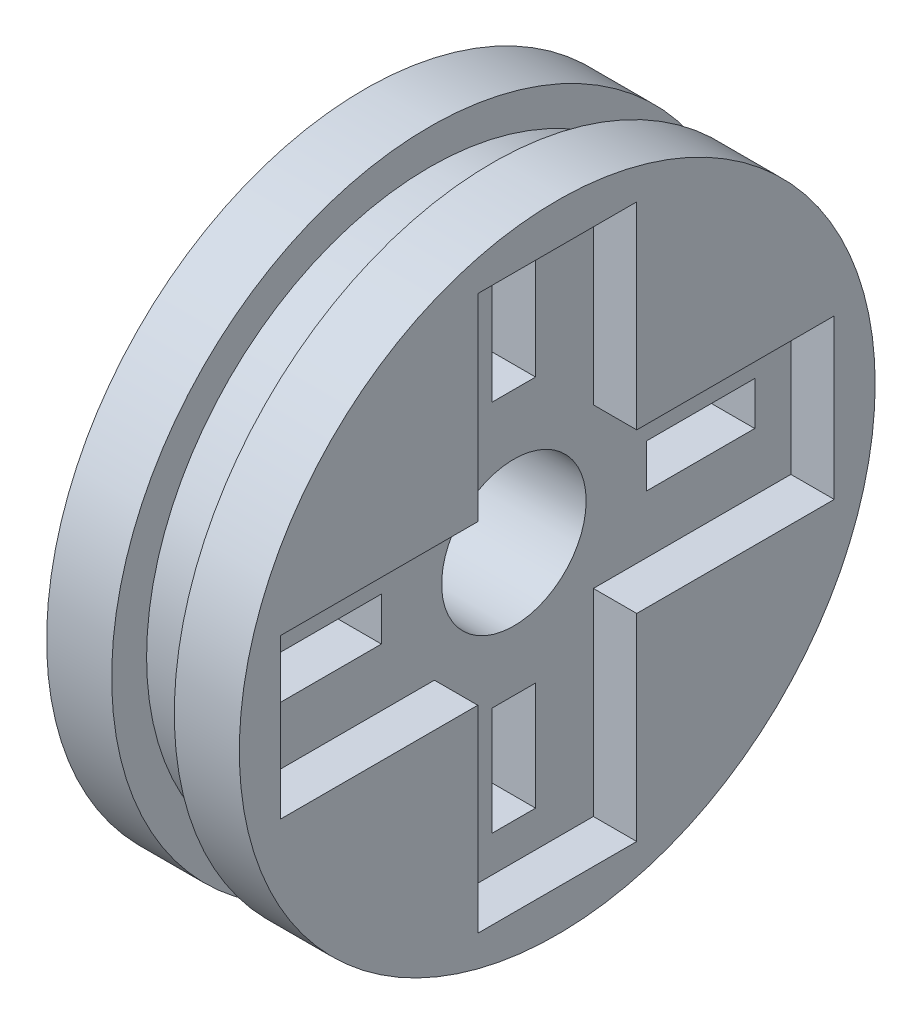
SolidWorks part; units mm, degrees
ref_plane "Front Plane" through (0, 0, 0) normal (0, 0, 1) x (1, 0, 0)
ref_plane "Top Plane" through (0, 0, 0) normal (0, 1, 0) x (1, 0, 0)
ref_plane "Right Plane" through (0, 0, 0) normal (1, 0, 0) x (0, 0, -1)
sketch "Sketch1" plane through (0, 0, 0) normal (1, 0, 0) x (0, 0, -1)
  circle A0 centre (-66, -65) radius 13.2
extrude "Boss-Extrude1" add sketch "Sketch1" along normal blind 8 from offset 85.2 offset against normal yes
sketch "Sketch2" plane through (0, 0, 0) normal (1, 0, 0) x (0, 0, -1)
  circle A0 centre (-66, -65) radius 20
extrude "Boss-Extrude2" add sketch "Sketch2" along normal blind 2.6 from offset 82.5 separate body offset against normal yes
combine bodies "Combine1" operation type subtract main body 101 bodies to subtract 102
sketch "Sketch3" plane through (0, 0, 0) normal (1, 0, 0) x (0, 0, -1)
  circle A0 centre (-66, -65) radius 11.75
extrude "Boss-Extrude3" add sketch "Sketch3" along normal blind 2.6 from offset 82.5 offset against normal yes
sketch "Sketch4" plane through (0, 0, 0) normal (1, 0, 0) x (0, 0, -1)
  circle A0 centre (-66, -65) radius 4.6
extrude "Boss-Extrude4" add sketch "Sketch4" along normal blind 2.3 from offset 79 separate body offset against normal yes
combine bodies "Combine2" operation type subtract main body 105 bodies to subtract 106
sketch "Sketch5" plane through (0, 0, 0) normal (0, 0, 1) x (1, 0, 0)
  line L1 (-79, -65) -> (-76.7, -65)
  line L2 (-79, -65) -> (-79, -53.5)
  line L3 (-79, -53.5) -> (-76.7, -53.5)
  line L4 (-76.7, -65) -> (-76.7, -53.5)
extrude "Boss-Extrude5" add sketch "Sketch5" along normal blind 6.6 from offset 62.7 separate body
combine bodies "Combine3" operation type subtract main body 107 bodies to subtract 108
sketch "Sketch6" plane through (0, 0, 0) normal (0, 0, 1) x (1, 0, 0)
  line L1 (-86.2, -59.5) -> (-76.2, -59.5)
  line L2 (-86.2, -59.5) -> (-86.2, -55)
  line L3 (-86.2, -55) -> (-76.2, -55)
  line L4 (-76.2, -59.5) -> (-76.2, -55)
extrude "Boss-Extrude6" add sketch "Sketch6" along normal blind 1.8 from offset 65.1 separate body
combine bodies "Combine4" operation type subtract main body 109 bodies to subtract 110
sketch "Sketch7" plane through (0, 0, 0) normal (0, 0, 1) x (1, 0, 0)
  line L1 (-79, -76.5) -> (-76.7, -76.5)
  line L2 (-79, -76.5) -> (-79, -65)
  line L3 (-79, -65) -> (-76.7, -65)
  line L4 (-76.7, -76.5) -> (-76.7, -65)
extrude "Boss-Extrude7" add sketch "Sketch7" along normal blind 6.6 from offset 62.7 separate body
combine bodies "Combine5" operation type subtract main body 111 bodies to subtract 112
sketch "Sketch8" plane through (0, 0, 0) normal (0, 0, 1) x (1, 0, 0)
  line L1 (-86.2, -75) -> (-76.2, -75)
  line L2 (-86.2, -75) -> (-86.2, -70.5)
  line L3 (-86.2, -70.5) -> (-76.2, -70.5)
  line L4 (-76.2, -75) -> (-76.2, -70.5)
extrude "Boss-Extrude8" add sketch "Sketch8" along normal blind 1.8 from offset 65.1 separate body
combine bodies "Combine6" operation type subtract main body 113 bodies to subtract 114
sketch "Sketch9" plane through (0, 0, 0) normal (0, 0, 1) x (1, 0, 0)
  line L1 (-79, -68.3) -> (-76.7, -68.3)
  line L2 (-79, -68.3) -> (-79, -61.7)
  line L3 (-79, -61.7) -> (-76.7, -61.7)
  line L4 (-76.7, -68.3) -> (-76.7, -61.7)
extrude "Boss-Extrude9" add sketch "Sketch9" along normal blind 11.5 from offset 66 separate body
combine bodies "Combine7" operation type subtract main body 115 bodies to subtract 116
sketch "Sketch10" plane through (0, 0, 0) normal (0, 0, 1) x (1, 0, 0)
  line L1 (-86.2, -65.9) -> (-76.2, -65.9)
  line L2 (-86.2, -65.9) -> (-86.2, -64.1)
  line L3 (-86.2, -64.1) -> (-76.2, -64.1)
  line L4 (-76.2, -65.9) -> (-76.2, -64.1)
extrude "Boss-Extrude10" add sketch "Sketch10" along normal blind 4.5 from offset 71.5 separate body
combine bodies "Combine8" operation type subtract main body 117 bodies to subtract 118
sketch "Sketch11" plane through (0, 0, 0) normal (0, 0, 1) x (1, 0, 0)
  line L1 (-79, -68.3) -> (-76.7, -68.3)
  line L2 (-79, -68.3) -> (-79, -61.7)
  line L3 (-79, -61.7) -> (-76.7, -61.7)
  line L4 (-76.7, -68.3) -> (-76.7, -61.7)
extrude "Boss-Extrude11" add sketch "Sketch11" along normal blind 11.5 from offset 54.5 separate body
combine bodies "Combine9" operation type subtract main body 119 bodies to subtract 120
sketch "Sketch12" plane through (0, 0, 0) normal (0, 0, 1) x (1, 0, 0)
  line L1 (-86.2, -65.9) -> (-76.2, -65.9)
  line L2 (-86.2, -65.9) -> (-86.2, -64.1)
  line L3 (-86.2, -64.1) -> (-76.2, -64.1)
  line L4 (-76.2, -65.9) -> (-76.2, -64.1)
extrude "Boss-Extrude12" add sketch "Sketch12" along normal blind 4.5 from offset 56 separate body
combine bodies "Combine10" operation type subtract main body 121 bodies to subtract 122
sketch "Sketch13" plane through (0, 0, 0) normal (1, 0, 0) x (0, 0, -1)
  circle A0 centre (-66, -65) radius 3
extrude "Boss-Extrude13" add sketch "Sketch13" along normal blind 10 from offset 86.2 separate body offset against normal yes
combine bodies "Combine11" operation type subtract main body 123 bodies to subtract 124
